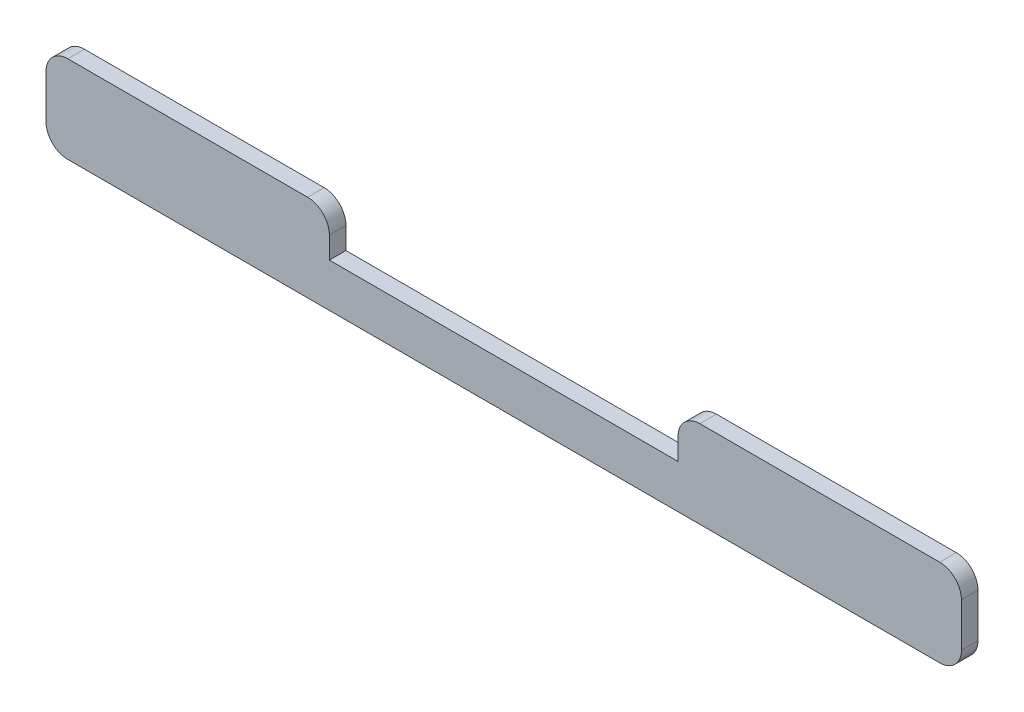
SolidWorks part; units mm, degrees
ref_plane "Front Plane" through (0, 0, 0) normal (0, 0, 1) x (1, 0, 0)
ref_plane "Top Plane" through (0, 0, 0) normal (0, 1, 0) x (1, 0, 0)
ref_plane "Right Plane" through (0, 0, 0) normal (1, 0, 0) x (0, 0, -1)
sketch "Sketch1" plane through (0, 0, 0) normal (0, 0, 1) x (1, 0, 0)
  line L1 (6.35, 0) -> (260.35, 0)
  line L2 (0, 6.35) -> (0, 19.05)
  line L3 (190.5, 25.4) -> (260.35, 25.4)
  line L4 (266.7, 6.35) -> (266.7, 19.05)
  line L5 (82.55, 12.7) -> (184.15, 12.7)
  line L6 (82.55, 12.7) -> (82.55, 19.05)
  line L7 (6.35, 25.4) -> (76.2, 25.4)
  line L8 (184.15, 12.7) -> (184.15, 19.05)
  line L11 (82.55, 12.7) -> (82.55, 19.05)
  arc A0 (260.35, 25.4) -> (266.7, 19.05) centre (260.35, 19.05) cw
  arc A1 (266.7, 6.35) -> (260.35, 0) centre (260.35, 6.35) cw
  arc A2 (0, 6.35) -> (6.35, 0) centre (6.35, 6.35) ccw
  arc A3 (6.35, 25.4) -> (0, 19.05) centre (6.35, 19.05) ccw
  arc A4 (190.5, 25.4) -> (184.15, 19.05) centre (190.5, 19.05) ccw
  arc A5 (76.2, 25.4) -> (82.55, 19.05) centre (76.2, 19.05) cw
  point P7 (266.7, 25.4)
  point P10 (266.7, 0)
  point P13 (0, 0)
  point P16 (0, 25.4)
  point P17 (133.35, 19.05)
  dimension "D3" = 6.35
  dimension "D4" = 6.35
  dimension "D1" = 266.7
  dimension "D2" = 25.4
  dimension "D5" = 101.6
  dimension "D6" = 133.35
extrude "Boss-Extrude1" add sketch "Sketch1" along normal blind 4.826 contours A5 L7 A3 L2 A2 L1 A1 L4 A0 L3 A4 L8 L5 L6 region at (133.35, 11.1557, 0)
equation "\"MDF\"= 0.19in"
equation "\"PVCID\" = 2.067in"
equation "\"PVCOD\" = 2.375in"
equation "\"GenDiameter\"= 60mm"
equation "\"GenCutDiameter\" = 1.8in"
equation "\"GenCutDistance\" = 1"
equation "\"TowerHeight\" = 6in"
equation "\"TowerFrontBase\" = 3in"
equation "\"FunnelHeight\" = 1in"
equation "\"FunnelAngle\" = 20"
equation "\"TowerSideBase\" = 3in"
equation "\"TowerPanelLength\" = 2in"
equation "\"TowerPanelLeeway\" = 0.5in"
equation "\"BaseLength\" = 9in"
equation "\"BaseWidth\" = 10in"
equation "\"WheelHoleLength\" = 3.25in"
equation "\"WheelHoleWidth\" = 26mm"
equation "\"WheelHoleFromBack\" = 1.5in"
equation "\"DropLength\" = 1in"
equation "\"DropWidth\" = 8.5in"
equation "\"BumperWidth\" = 1in"
equation "\"SmallHexDiameter\" = 0.185in"
equation "\"SmallHexHeight\" = 0.701in"
equation "\"ScrewSize\" = 0.106in"
equation "\"BigHexDiameter\" = 0.251in"
equation "\"BigHexHeight\" = 0.374in"
equation "\"PCBThickness\" = 0.066in"
equation "\"ConnectorHeight\" = 0.517in"
equation "\"BoardHeight\" = 0.583in"
equation "\"UnoStackHeight\" = 1.351in"
equation "\"UnoStackWidth\" = 3.053in"
equation "\"UnoStackLength\" = 3.152in"
equation "\"HBridgeWidth\" = 1.797in"
equation "\"HBridgeLength\" = 2.236in"
equation "\"DSWidth\" = 1.820in"
equation "\"DSLength\" = 1.833in"
equation "\"StepperWidth\" = 1.799in"
equation "\"StepperLength\" = 2.248in"
equation "\"ULNWidth\" = 1.304in"
equation "\"ULNLength\" = 1.545in"
equation "\"VSwitchHeight\" = 0.392in"
equation "\"VSwitchWidth\" = 0.637in"
equation "\"VSwitchLength\" = 1.097in"
equation "\"SkateWheelDiameter\" = 80mm"
equation "\"SkateWheelThickness\" = 24mm"
equation "\"BaseDistance\" = 3in"
equation "\"DummyVar\" = 2in"
equation "\"D1@Boss-Extrude1\"=\"MDF\""
